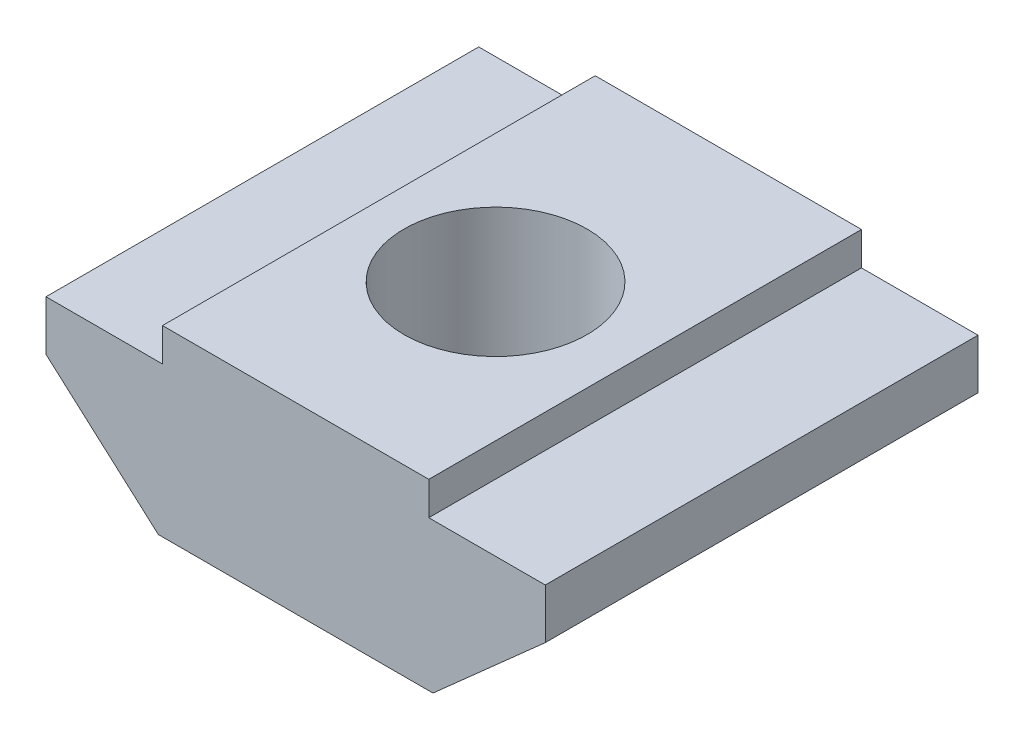
SolidWorks part; units mm, degrees
ref_plane "Спереди" through (0, 0, 0) normal (0, 0, 1) x (1, 0, 0)
ref_plane "Сверху" through (0, 0, 0) normal (0, 1, 0) x (1, 0, 0)
ref_plane "Справа" through (0, 0, 0) normal (1, 0, 0) x (0, 0, -1)
sketch "Эскиз1" plane through (0, 0, 0) normal (0, 0, 1) x (1, 0, 0)
  line L0 (-4.4619, 0) -> (3.7881, 0)
  line L2 (-4.4619, 0) -> (-7.8369, 3)
  line L3 (-7.8369, 3) -> (-7.8369, 4.5)
  line L4 (-7.8369, 4.5) -> (-4.3369, 4.5)
  line L5 (-4.3369, 4.5) -> (-4.3369, 5.5)
  line L6 (-4.3369, 5.5) -> (3.6631, 5.5)
  line L7 (3.6631, 5.5) -> (3.6631, 4.5)
  line L8 (3.6631, 4.5) -> (7.1631, 4.5)
  line L9 (7.1631, 4.5) -> (7.1631, 3)
  line L11 (3.7881, 0) -> (7.1631, 3)
  point P3 (-0.9835, 0)
  dimension "D1" = 8
  dimension "D2" = 8.25
  dimension "D3" = 1
  dimension "D4" = 15
  dimension "D5" = 1.5
  dimension "D6" = 5.5
  dimension "D7" = 0
  dimension "D8" = 3.6631
  dimension "D11" = 0.9835
extrude "Бобышка-Вытянуть1" add sketch "Эскиз1" along normal blind 13
hole_wizard "Зенковка для  винта с плоской головкой M52" positions "Трехмерный эскиз1" profile "Эскиз4" countersink size "M5" standard "Ansi Metric" end condition through all
sketch3d "Трехмерный эскиз1"
  point P1 (-0.4718, 5.5, 6.8592)
sketch "Эскиз4" plane through (-0.4718, 5.5, 6.8592) normal (1, 0, 0) x (0, 0, 1)
  line L0 (0, 0) -> (0, 5.5)
  line L1 (0, 5.5) -> (2.75, 5.5)
  line L2 (2.75, 5.5) -> (2.75, 2.45)
  line L3 (2.75, 2.45) -> (2.75, 0)
  line L5 (2.75, 0) -> (0, 0)
  line L6 (-2.75, 2.45) -> (-2.75, 0) construction
  line L11 (0, -6.35) -> (0, 107.95) construction
  dimension "Диаметр сквозного отверстия" = 5.5
  dimension "Глубина сквозного отверстия" = 5.5
  dimension "Диаметр передней зенковки" = 5.5
